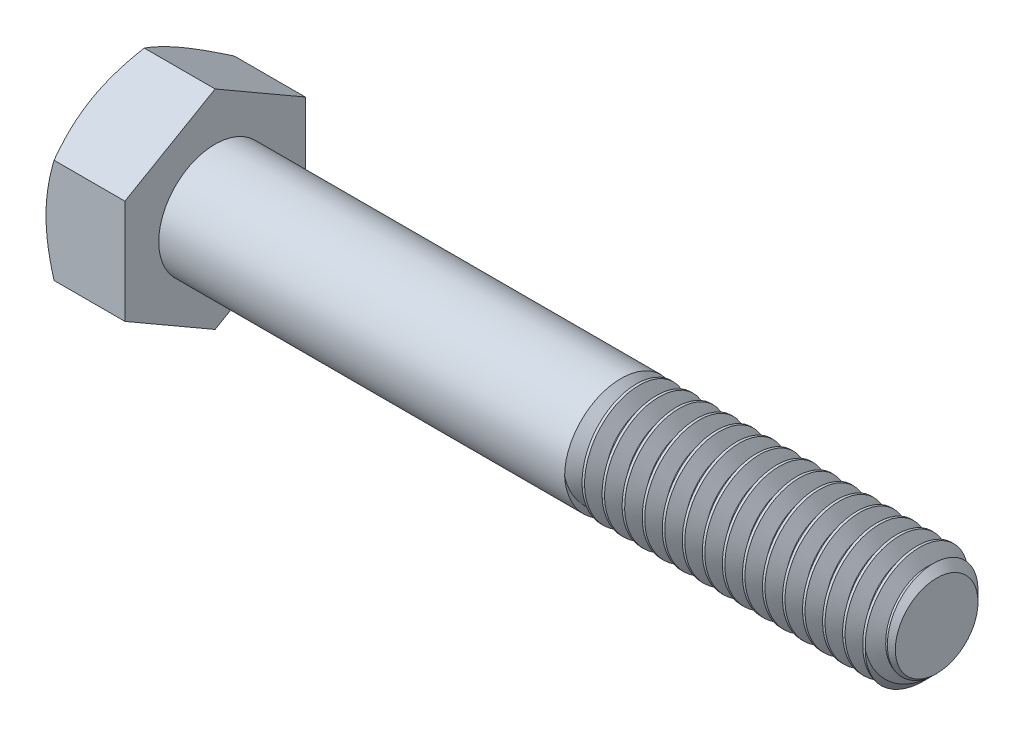
SolidWorks part; units mm, degrees
note: '?' marks a value the reader was unsure of.
ref_plane "Front Plane" through (0, 0, 0) normal (0, 0, 1) x (1, 0, 0)
ref_plane "Top Plane" through (0, 0, 0) normal (0, 1, 0) x (1, 0, 0)
ref_plane "Right Plane" through (0, 0, 0) normal (1, 0, 0) x (0, 0, -1)
sketch "Sketch1" plane through (0, 0, 0) normal (0, 0, 1) x (1, 0, 0)
  line L0 (-28.1781, 0) -> (28.1781, 0) construction
  line L1 (28.1781, 3.9688) -> (28.1781, -3.9688) construction
  line L2 (-22.6219, 6.35) -> (-22.6219, -6.35) construction
  line L3 (-28.1781, 6.35) -> (-28.1781, -6.35) construction
  point P9 (-22.6219, 0)
  point P10 (23.2392, -3.9688)
  dimension "D1" = 4.9389
  dimension "Screw Dia" = 7.9375
  dimension "Hex" = 12.7
  dimension "Head Ht" = 5.5562
  dimension "Screw Lenght" = 50.8
ref_plane "Plane2" through (28.1781, 0, 0) normal (1, 0, 0) x (0, 0, -1)
sketch "Sketch5" plane through (28.1781, 0, 0) normal (1, 0, 0) x (0, 0, -1)
  circle A0 centre (0, 0) radius 3.9688
extrude "Boss-Extrude3" add sketch "Sketch5" against normal up to vertex (50.8 mm away) up to point (-22.6219, 0, 0)
sketch "Sketch9" plane through (28.1781, 0, 0) normal (1, 0, 0) x (0, 0, -1)
  circle A1 centre (0, 0) radius 3.9688
  circle A2 centre (0, 0) radius 3.9688
  dimension "D1" = 0
curve "Helix/Spiral1" pitch 1.4111 height 23.6361 turns 16.75 parameters "Pitch"=1.4111
chamfer "Chamfer1" distance 1.0583 angle 45 1 edges at (28.1781, 0, -3.9688)
sketch "Sketch10" plane through (0, 0, 0) normal (0, 0, 1) x (1, 0, 0)
  line L0 (28.1781, 3.9688) -> (28.7073, 3.0522)
  line L1 (28.7073, 3.0522) -> (28.8837, 3.0522)
  line L2 (28.8837, 3.0522) -> (29.4128, 3.9688)
  line L3 (28.1781, 3.9688) -> (29.4128, 3.9688)
  line L4 (28.7955, 3.9688) -> (28.7955, 3.0522) construction
  line L5 (28.4427, 3.5105) -> (29.1483, 3.5105) construction
  dimension "D1" = 60
  dimension "D2" = 0.1764
  dimension "D3" = 0.7056
sweep "Cut-Sweep1" cut profiles "Sketch10" path "Helix/Spiral1"
sketch "Sketch11" plane through (0, 0, 0) normal (0, 0, 1) x (1, 0, 0)
  line L0 (-22.6219, 3.9688) -> (-22.6219, 0)
  line L1 (-22.6219, 0) -> (9.9219, 0)
  line L3 (9.9219, 0) -> (5.9531, 3.9688)
  line L4 (-22.6219, 3.9688) -> (5.9531, 3.9688)
  dimension "D1" = 45
  dimension "MIn Thread" = 22.225
revolve "Revolve1" add sketch "Sketch11" angle 360 about L1
sketch "Sketch6" plane through (-22.6219, 0, 0) normal (-1, 0, 0) x (0, 0, 1)
  line L0 (0, 6.35) -> (0, -6.35) construction
  line L1 (6.35, 3.6662) -> (0, 7.3323)
  line L2 (0, 7.3323) -> (-6.35, 3.6662)
  line L3 (-6.35, 3.6662) -> (-6.35, -3.6662)
  line L4 (-6.35, -3.6662) -> (0, -7.3323)
  line L5 (0, -7.3323) -> (6.35, -3.6662)
  line L6 (6.35, -3.6662) -> (6.35, 3.6662)
  circle A0 centre (0, 0) radius 6.35 construction
extrude "Boss-Extrude4" add sketch "Sketch6" along normal up to vertex (5.5563 mm away) up to point (-28.1781, -6.35, 0)
sketch "Sketch7" plane through (-28.1781, 0, 0) normal (-1, 0, 0) x (0, 0, 1)
  circle A0 centre (0, 0) radius 6.35 construction
  circle A1 centre (0, 0) radius 6.35
sketch "Sketch8" plane through (-28.1781, 0, 0) normal (-1, 0, 0) x (0, 0, 1)
  circle A0 centre (0, 0) radius 6.35 construction
  circle A1 centre (0, 0) radius 6.35
extrude "Cut-Extrude3" cut sketch "Sketch8" against normal through all draft 60 flip side to cut
ref_axis "Bolt Axis" through (-22.6219, 0, 0) along (1, 0, 0)?
equation "\"D2@Sketch10\" = \"Pitch@Helix/Spiral1\"*.125"
equation "\"D3@Sketch10\" = \"Pitch@Helix/Spiral1\"*.5"
equation "\"D3@Helix/Spiral1\" = \"MIn Thread@Sketch11\"+\"Pitch@Helix/Spiral1\""
equation "\"D1@Chamfer1\" = \"Pitch@Helix/Spiral1\"*.75"
equation "\"D1@Sketch1\" = \"Pitch@Helix/Spiral1\"*3.5"
